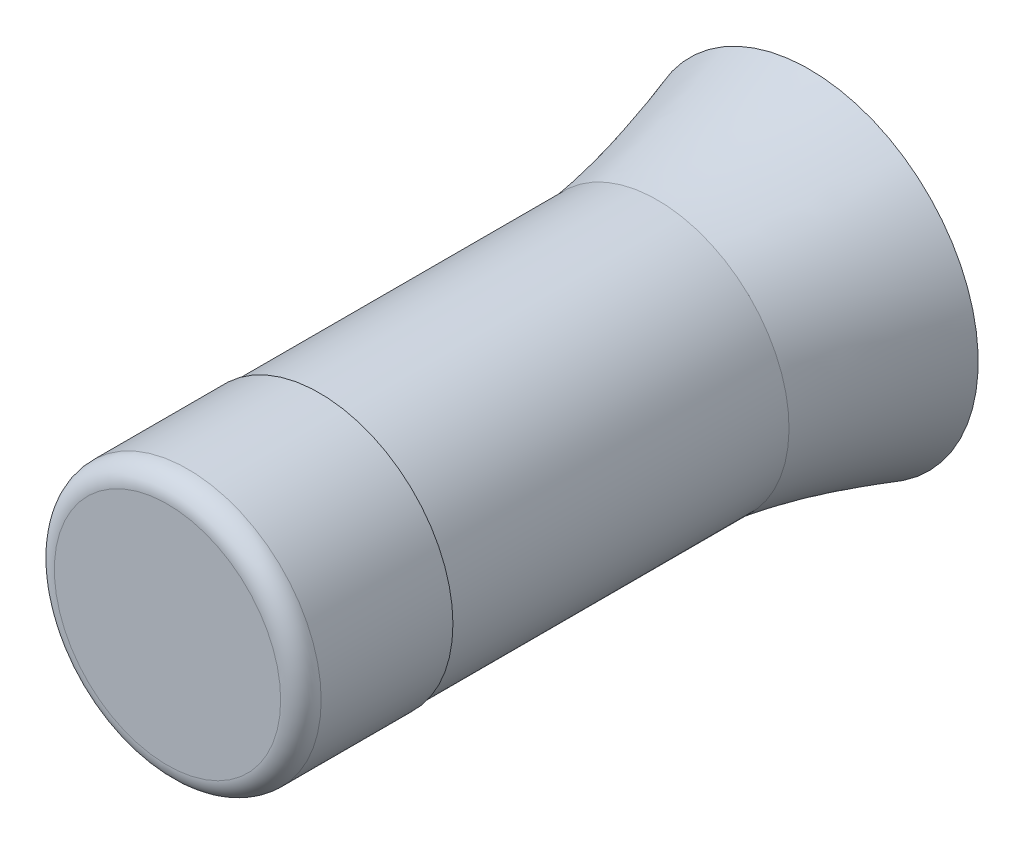
SolidWorks part; units mm, degrees
ref_plane "정면" through (0, 0, 0) normal (0, 0, 1) x (1, 0, 0)
ref_plane "윗면" through (0, 0, 0) normal (0, 1, 0) x (1, 0, 0)
ref_plane "우측면" through (0, 0, 0) normal (1, 0, 0) x (0, 0, -1)
sketch "스케치1" plane through (0, 0, 0) normal (0, 0, 1) x (1, 0, 0)
  circle A0 centre (0, 0) radius 1.95
  dimension "D1" = 3.9
extrude "보스-돌출1" add sketch "스케치1" along normal blind 5
sketch "스케치2" plane through (0, 0, 0) normal (0, 0, -1) x (-1, 0, 0)
  circle A1 centre (0, 0) radius 1.95
  circle A2 centre (0, 0) radius 1.95
  dimension "D1" = 0
ref_plane "평면1" through (0, 0, -2.25) normal (0, 0, -1) x (-1, 0, 0)
sketch "스케치3" plane through (0, 0, -2.25) normal (0, 0, -1) x (-1, 0, 0)
  circle A0 centre (0, 0) radius 2.5
  dimension "D1" = 5
loft "로프트1" add profiles "스케치2", "스케치3" connector at (1.3579, 1.3995, 0) connector at (2.3414, 0.8763, -2.25)
sketch "스케치4" plane through (0, 0, 5) normal (0, 0, 1) x (1, 0, 0)
  circle A0 centre (0, 0) radius 1.975
  dimension "D1" = 3.95
extrude "보스-돌출2" add sketch "스케치4" along normal blind 2.25
fillet "필렛1" radius 0.3 1 edges at (1.975, 0, 7.25)
